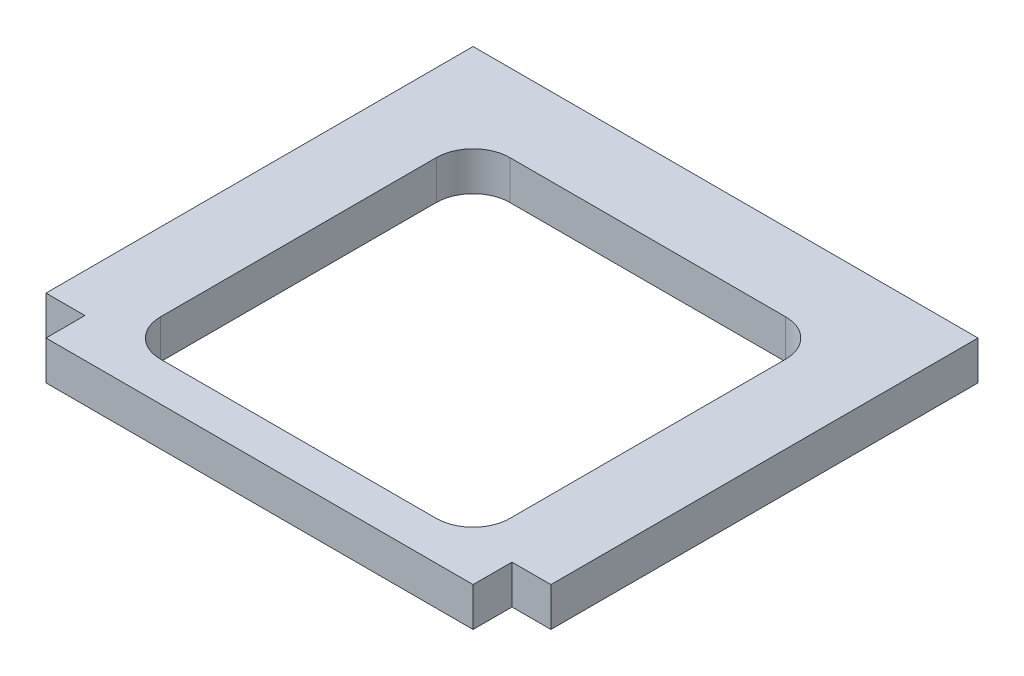
SolidWorks part; units mm, degrees
ref_plane "Front Plane" through (0, 0, 0) normal (0, 0, 1) x (1, 0, 0)
ref_plane "Top Plane" through (0, 0, 0) normal (0, 1, 0) x (1, 0, 0)
ref_plane "Right Plane" through (0, 0, 0) normal (1, 0, 0) x (0, 0, -1)
sketch "Sketch1" plane through (0, 0, 0) normal (0, 1, 0) x (1, 0, 0)
  line L0 (-41.2, -28.5) -> (-41.2, 41.2)
  line L1 (-22.5, -28.5) -> (22.5, -28.5)
  line L2 (-28.5, -22.5) -> (-28.5, 22.5)
  line L3 (-22.5, 28.5) -> (22.5, 28.5)
  line L4 (28.5, -22.5) -> (28.5, 22.5)
  line L5 (-28.5, -28.5) -> (28.5, 28.5) construction
  line L6 (-28.5, 28.5) -> (28.5, -28.5) construction
  line L7 (-41.2, 41.2) -> (41.2, 41.2)
  line L8 (41.2, -28.5) -> (41.2, 41.2)
  line L9 (28.5, -28.5) -> (28.5, 28.5) construction
  line L10 (-34.85, -34.85) -> (34.85, -34.85)
  line L11 (-41.2, -41.2) -> (-41.2, 41.2) construction
  line L12 (-41.2, -41.2) -> (41.2, -41.2) construction
  line L13 (41.2, -41.2) -> (41.2, 41.2) construction
  line L14 (-28.5, 28.5) -> (28.5, 28.5) construction
  line L15 (-28.5, -28.5) -> (28.5, -28.5) construction
  line L16 (-28.5, -28.5) -> (-28.5, 28.5) construction
  line L17 (-41.2, -28.5) -> (-34.85, -28.5)
  line L18 (-34.85, -34.85) -> (-34.85, -28.5)
  line L21 (41.2, -28.5) -> (34.85, -28.5)
  line L22 (34.85, -34.85) -> (34.85, -28.5)
  arc A0 (28.5, 22.5) -> (22.5, 28.5) centre (22.5, 22.5) ccw
  arc A1 (28.5, -22.5) -> (22.5, -28.5) centre (22.5, -22.5) cw
  arc A2 (-22.5, -28.5) -> (-28.5, -22.5) centre (-22.5, -22.5) cw
  arc A3 (-28.5, 22.5) -> (-22.5, 28.5) centre (-22.5, 22.5) cw
  point P0 (0, 0)
  dimension "D7" = 6
  dimension "D1" = 57
  dimension "D2" = 57
  dimension "D4" = 6.35
  dimension "D5" = 6.35
  dimension "D6" = 6.35
  dimension "D3" = 12.7
extrude "Boss-Extrude1" add sketch "Sketch1" along normal blind 6.35
